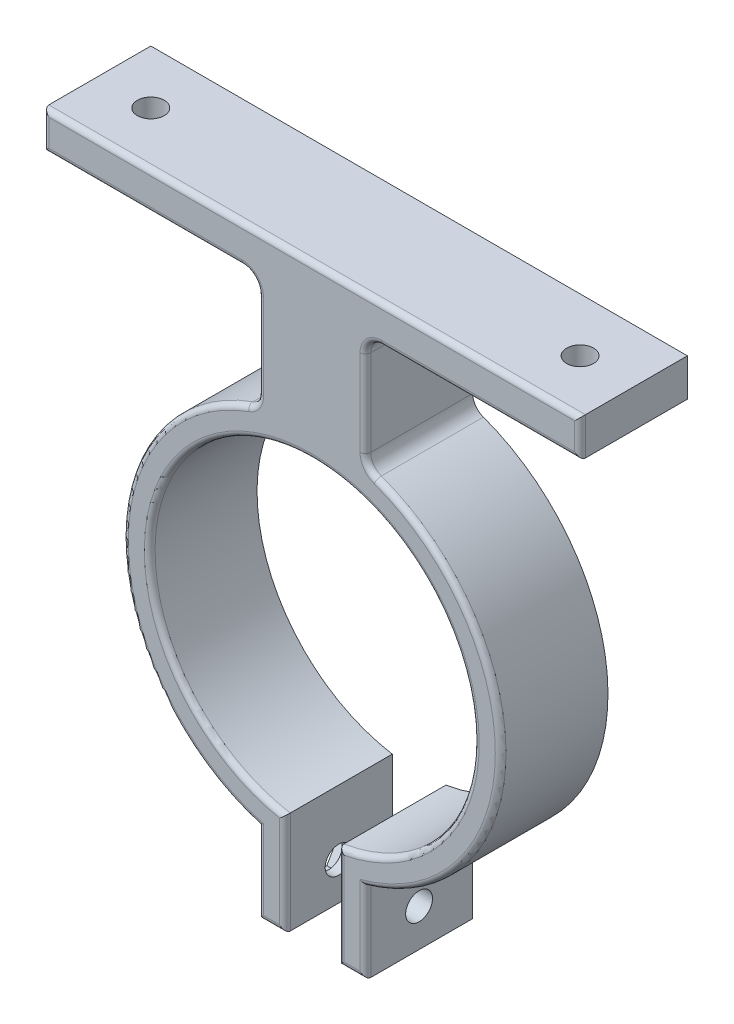
SolidWorks part; units mm, degrees
ref_plane "Front Plane" through (0, 0, 0) normal (0, 0, 1) x (1, 0, 0)
ref_plane "Top Plane" through (0, 0, 0) normal (0, 1, 0) x (1, 0, 0)
ref_plane "Right Plane" through (0, 0, 0) normal (1, 0, 0) x (0, 0, -1)
sketch "Sketch1" plane through (0, 0, 0) normal (0, 0, 1) x (1, 0, 0)
  line L0 (0, -240.3264) -> (0, 11775.9931) construction
  line L1 (5, -29.7832) -> (5, -48.8332)
  line L2 (-5, -29.7832) -> (-5, -48.8332)
  line L3 (10, -33.7497) -> (10, -48.8332)
  line L4 (-10, -33.7497) -> (-10, -48.8332)
  line L5 (10, -48.8332) -> (5, -48.8332)
  line L6 (5, -48.8332) -> (4.7317, -48.6894)
  line L7 (-5, -48.8332) -> (-10, -48.8332)
  line L8 (-10, -48.8332) -> (-10.1837, -48.5756)
  line L9 (-50, 55) -> (-10, 55)
  line L10 (-50, 62) -> (50, 62)
  line L11 (-50, 62) -> (-50, 55)
  line L12 (10, 55) -> (50, 55)
  line L13 (50, 62) -> (50, 55)
  line L14 (-1000, 30.2) -> (49000, 30.2) construction
  line L15 (-10, 55) -> (-10, 33.7497)
  line L16 (10, 55) -> (10, 33.7497)
  line L17 (0, 0) -> (5, -29.7832) construction
  line L18 (5, -29.7832) -> (4.9202, -29.744) construction
  line L19 (0, 0) -> (-5, -29.7832) construction
  line L20 (-1000, 0) -> (49000, 0) construction
  arc A0 (5, -29.7832) -> (-5, -29.7832) centre (0, 0) ccw
  arc A1 (10, -33.7497) -> (10, 33.7497) centre (0, 0) ccw
  arc A2 (-10, 33.7497) -> (-10, -33.7497) centre (0, 0) ccw
  arc A4 (10, -33.7497) -> (-10, -33.7497) centre (0, 0) ccw construction
  point P24 (0, 30.2)
  dimension "D1" = 5
  dimension "D5" = 30.2
  dimension "D2" = 5
  dimension "D3" = 19.05
  dimension "D4" = 19.05
  dimension "D7" = 50
  dimension "D8" = 50
  dimension "D9" = 62
  dimension "D10" = 10
  dimension "D11" = 7
  dimension "D12" = 19.06
  dimension "D6" = 5
extrude "Boss-Extrude1" add sketch "Sketch1" along normal blind 20 contours L12 A2 L4 L7 L2 A0 L1 L5 L3 A1 L13 L10 L11 region at (0, 31.6928, 0)
fillet "Fillet1" radius 3 4 edges at (10, 33.7497, 10) (10, 55, 10) (-10, 33.7497, 10) (-10, 55, 10)
ref_plane "Plane1" through (0, 55, 0) normal (0, -1, 0) x (-1, 0, 0)
sketch "Sketch2" plane through (0, 55, 0) normal (0, -1, 0) x (-1, 0, 0)
  line L0 (-13, -20) -> (-50, -20) construction
  line L1 (50, -20) -> (50, 0) construction
  line L5 (-50, -20) -> (-50, 0) construction
  line L6 (-13, -20) -> (-50, -20) construction
  circle A0 centre (40, -10) radius 2.5
  circle A1 centre (-40, -10) radius 2.5
  dimension "D1" = 10
  dimension "D3" = 10
  dimension "D2" = 10
  dimension "D4" = 10
extrude "Cut-Extrude1" cut sketch "Sketch2" against normal through all
ref_plane "Plane2" through (-10, 0, 0) normal (-1, 0, 0) x (0, 0, 1)
sketch "Sketch3" plane through (-10, 0, 0) normal (-1, 0, 0) x (0, 0, 1)
  line L0 (20, -33.7497) -> (20, -48.8332) construction
  line L2 (20, -48.8332) -> (0, -48.8332) construction
  line L4 (15.6003, -41.8332) -> (12.8001, -36.9832)
  line L5 (12.8001, -36.9832) -> (7.1999, -36.9832)
  line L6 (7.1999, -36.9832) -> (4.3997, -41.8332)
  line L7 (4.3997, -41.8332) -> (7.1999, -46.6832)
  line L8 (7.1999, -46.6832) -> (12.8001, -46.6832)
  line L9 (12.8001, -46.6832) -> (15.6003, -41.8332)
  circle A0 centre (10, -41.8332) radius 2.5
  circle A1 centre (10, -41.8332) radius 4.85 construction
  dimension "D1" = 10
  dimension "D3" = 9.7
  dimension "D2" = 7
extrude "Cut-Extrude2" cut sketch "Sketch3" against normal through all contours A0 region at (-10, -41.8332, 10)
extrude "Cut-Extrude3" cut sketch "Sketch3<4>" against normal blind 3.175
sketch "Sketch3<4>" plane through (-10, 0, 0) normal (-1, 0, 0) x (0, 0, 1) same geometry as "Sketch3"
fillet "Fillet2" radius 1 20 edges at (-50, 58.5, 20) (0, 62, 20) (50, 58.5, 20) (31.5, 55, 20) (10.8787, 54.1213, 20) (10, 43.96, 20) (10.5441, 34.197, 20) (35.1846, -1.0416, 20) (10, -41.2914, 20) (7.5, -48.8332, 20) (5, -39.3082, 20) (0, 30.2, 20) (-5, -39.3082, 20) (-7.5, -48.8332, 20) (-10, -41.2914, 20) (-35.1846, -1.0416, 20) (-10.5441, 34.197, 20) (-10, 43.96, 20) (-10.8787, 54.1213, 20) (-31.5, 55, 20)
